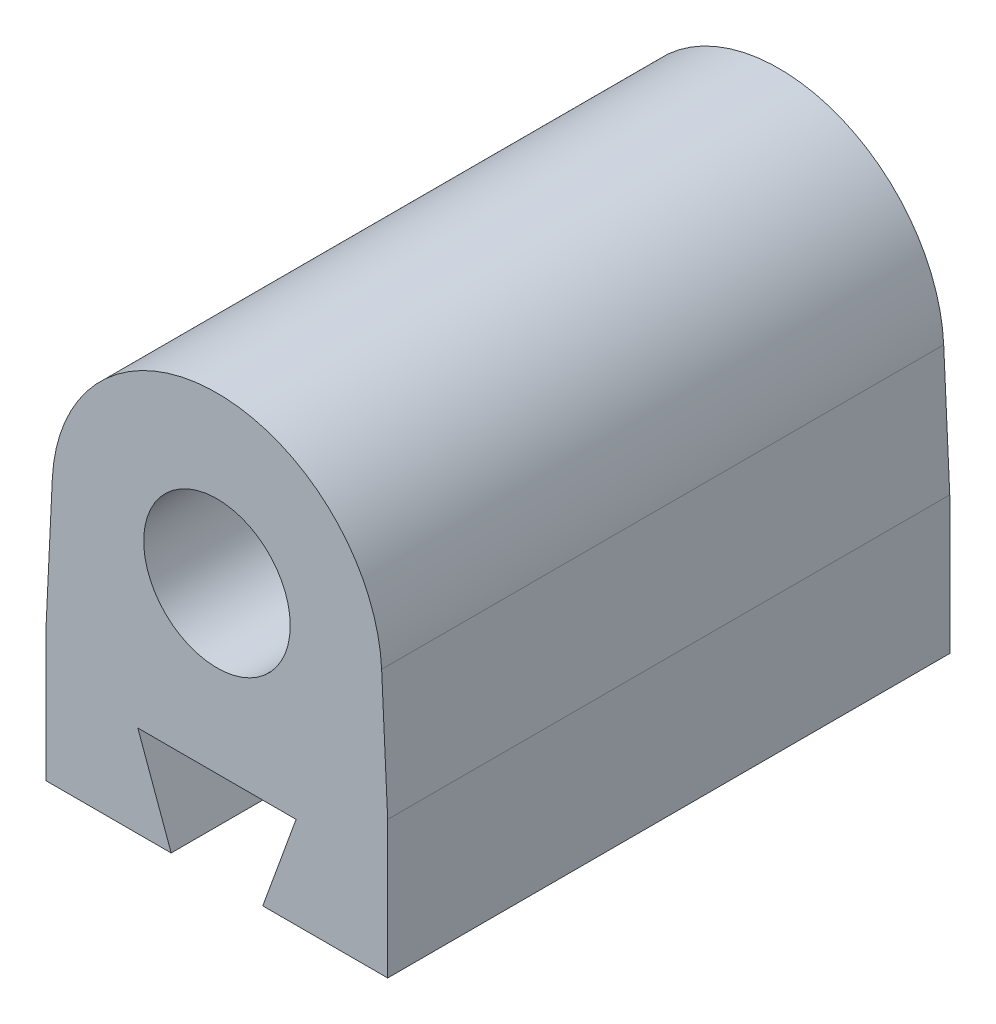
SolidWorks part; units mm, degrees
material "ABS"
ref_plane "Front Plane" through (0, 0, 0) normal (0, 0, 1) x (1, 0, 0)
ref_plane "Top Plane" through (0, 0, 0) normal (0, 1, 0) x (1, 0, 0)
ref_plane "Right Plane" through (0, 0, 0) normal (1, 0, 0) x (0, 0, -1)
sketch "Sketch1" plane through (0, 0, 0) normal (0, 0, 1) x (1, 0, 0)
  line L0 (-23.6397, 0) -> (-27.2794, 10)
  line L1 (-27.2794, 10) -> (-10, 10)
  line L2 (-10, 10) -> (-13.6397, 0)
  line L3 (-13.6397, 0) -> (0, 0)
  line L4 (0, 0) -> (0, 15)
  line L5 (0, 15) -> (-37.2794, 15)
  line L6 (-37.2794, 15) -> (-37.2794, 0)
  line L7 (-37.2794, 0) -> (-23.6397, 0)
  line L8 (-37.2794, 15) -> (-36.6193, 28.8565)
  line L9 (0, 15) -> (-0.6601, 28.8565)
  line L10 (-18.6397, 28) -> (-18.6397, 15)
  circle A0 centre (-18.6397, 28) radius 8
  circle A1 centre (-18.6397, 28) radius 18
  dimension "D8" = 16
  dimension "D1" = 70
  dimension "D2" = 70
  dimension "D3" = 10
  dimension "D4" = 5
  dimension "D5" = 10
  dimension "D6" = 10
  dimension "D7" = 10
  dimension "D9" = 10
extrude "Boss-Extrude1" add sketch "Sketch1" along normal blind 61.37 contours A1 L5 L6 L7 L0 L1 | A1 L8 L5 | A1 L5 A0 | A1 L1 L2 L3 L4 L5 | A1 L5 L9 | L5 A1 | A1 | A0 region at (-31.4731, 6.9414, 0) region at (-5.8063, 6.9414, 0) region at (-18.6397, 12.9741, 0) region at (-35.3243, 18.3571, 0) region at (-34.9164, 21.5045, 0) region at (-1.9551, 18.3571, 0)
equation "\"D2@Sketch1\"=\"D1@Sketch1\""
equation "\"D6@Sketch1\"=\"D5@Sketch1\""
equation "\"D1@Boss-Extrude1\"= 68.00- 6.63"
